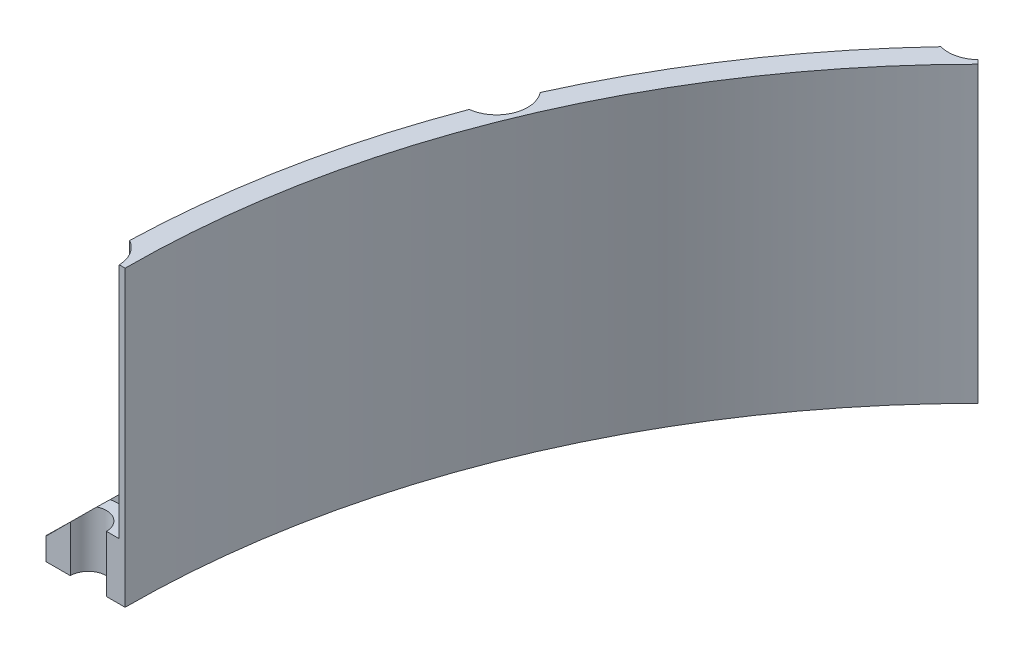
SolidWorks part; units mm, degrees
ref_plane "Front Plane" through (0, 0, 0) normal (0, 0, 1) x (1, 0, 0)
ref_plane "Top Plane" through (0, 0, 0) normal (0, 1, 0) x (1, 0, 0)
ref_plane "Right Plane" through (0, 0, 0) normal (1, 0, 0) x (0, 0, -1)
sketch "Sketch1" plane through (0, 0, 0) normal (0, 1, 0) x (1, 0, 0)
  line L0 (0, 0) -> (-77.15, 0) construction
  line L1 (0, 0) -> (0, 88.5692) construction
  line L2 (-53.3866, 53.3866) -> (-54.5533, 54.5533)
  line L3 (-75.5, 0) -> (-77.15, 0)
  line L4 (0, 0) -> (-104.3217, 43.2115) construction
  line L5 (0, 0) -> (-103.9733, 20.6816) construction
  line L6 (-55.6847, 55.6847) -> (-56.816, 56.816) construction
  line L7 (-56.816, 56.816) -> (-58.3363, 58.3363)
  line L8 (-54.5533, 54.5533) -> (-55.6847, 55.6847) construction
  line L9 (-78.75, 0) -> (-80.35, 0) construction
  line L10 (-80.35, 0) -> (-99.2871, 0) construction
  line L11 (-78.75, 0) -> (-80.35, 0) construction
  line L12 (-80.35, 0) -> (-82.5, 0)
  line L13 (-77.15, 0) -> (-78.75, 0) construction
  line L14 (-77.15, 0) -> (-78.75, 0) construction
  circle A0 centre (0, 0) radius 82.5 construction
  arc A1 (-82.5, 0) -> (-58.3363, 58.3363) centre (0, 0) cw
  arc A2 (-75.5, 0) -> (-53.3866, 53.3866) centre (0, 0) cw
  circle A3 centre (-72.7555, 30.1363) radius 1.6
  circle A4 centre (0, 0) radius 78.75 construction
  circle A5 centre (-77.2368, 15.3634) radius 1.25
  circle A6 centre (-65.4782, 43.7512) radius 1.25
  arc A7 (-80.35, 0) -> (-77.15, 0) centre (-78.75, 0) cw
  arc A8 (-56.816, 56.816) -> (-54.5533, 54.5533) centre (-55.6847, 55.6847) ccw
  arc A9 (-54.5419, 56.8045) -> (-56.816, 56.816) centre (-55.6847, 55.6847) ccw construction
  arc A10 (-54.5533, 54.5533) -> (-54.5419, 56.8045) centre (-55.6847, 55.6847) ccw construction
  arc A11 (-78.7337, -1.5999) -> (-80.35, 0) centre (-78.75, 0) cw construction
  arc A12 (-77.15, 0) -> (-78.7337, -1.5999) centre (-78.75, 0) cw construction
  dimension "D1" = 165
  dimension "D4" = 157.5
  dimension "D5" = 3.2
  dimension "D8" = 2.5
  dimension "D6" = 22.5
  dimension "D3" = 7
extrude "Boss-Extrude1" add sketch "Sketch1" along normal blind 2 contours A1 | A2 L3 A1 L2 region at (-71.209, 0, -29.4957)
sketch "Sketch2" plane through (0, 2, 0) normal (0, 1, 0) x (1, 0, 0)
  line L0 (-75.5, 0) -> (-77.15, 0)
  line L1 (-75.5, 0) -> (-77.15, 0) construction
  line L3 (-54.5533, 54.5533) -> (-53.3866, 53.3866)
  arc A2 (-55.3857, 54.1128) -> (-64.9332, 42.1949) centre (-0.0005, -0.04) ccw
  arc A3 (-77.4605, 0) -> (-54.773, 54.7325) centre (-0.0005, -0.04) ccw construction
  arc A6 (-71.897, 28.7862) -> (-77.4543, 0.9387) centre (-0.0005, -0.04) ccw construction
  arc A7 (-72.0793, 28.3273) -> (-76.1531, 14.1313) centre (-0.0005, -0.04) ccw
  arc A8 (-53.3866, 53.3866) -> (-75.5, 0) centre (0, 0) ccw construction
  arc A9 (-77.4605, 0) -> (-54.773, 54.7325) centre (-0.0005, -0.04) ccw construction
  arc A11 (-77.4605, 0) -> (-54.773, 54.7325) centre (-0.0005, -0.04) ccw construction
  arc A14 (-71.897, 28.7862) -> (-77.4543, 0.9387) centre (-0.0005, -0.04) ccw construction
  arc A15 (-64.9332, 42.1949) -> (-71.1934, 30.4825) centre (-0.0005, -0.04) ccw
  arc A17 (-71.897, 28.7862) -> (-77.4543, 0.9387) centre (-0.0005, -0.04) ccw construction
  arc A18 (-76.1531, 14.1313) -> (-77.4543, 0.9387) centre (-0.0005, -0.04) ccw
  circle A19 centre (-72.7555, 30.1363) radius 1.6 construction
  arc A20 (-71.897, 28.7862) -> (-71.1934, 30.4825) centre (-72.7555, 30.1363) ccw
  circle A21 centre (-77.2368, 15.3634) radius 1.25 construction
  circle A22 centre (-77.2368, 15.3634) radius 1.25 construction
  circle A23 centre (-65.4782, 43.7512) radius 1.25 construction
  circle A24 centre (-65.4782, 43.7512) radius 1.25 construction
  arc A25 (-71.1934, 30.4825) -> (-71.897, 28.7862) centre (-72.7555, 30.1363) ccw construction
  arc A26 (-71.1934, 30.4825) -> (-71.897, 28.7862) centre (-0.0005, -0.04) ccw construction
  arc A27 (-71.897, 28.7862) -> (-72.0793, 28.3273) centre (-0.0005, -0.04) ccw
  arc A28 (-71.1934, 30.4825) -> (-71.897, 28.7862) centre (-0.0005, -0.04) ccw construction
  arc A29 (-71.1934, 30.4825) -> (-71.897, 28.7862) centre (-0.0005, -0.04) ccw construction
  arc A30 (-71.1934, 30.4825) -> (-71.897, 28.7862) centre (-0.0005, -0.04) ccw construction
  arc A31 (-77.15, 0) -> (-80.35, 0) centre (-78.75, 0) ccw construction
  arc A32 (-77.15, 0) -> (-77.4543, 0.9387) centre (-78.75, 0) ccw
  arc A33 (-56.816, 56.816) -> (-54.5533, 54.5533) centre (-55.6847, 55.6847) ccw construction
  arc A34 (-55.3857, 54.1128) -> (-54.5533, 54.5533) centre (-55.6847, 55.6847) ccw
  arc A35 (-55.3857, 54.1128) -> (-71.1934, 30.4825) centre (-0.0005, -0.04) ccw construction
  arc A36 (-55.3857, 54.1128) -> (-71.1934, 30.4825) centre (-0.0005, -0.04) ccw construction
  arc A37 (-55.3857, 54.1128) -> (-71.1934, 30.4825) centre (-0.0005, -0.04) ccw construction
  arc A38 (-56.816, 56.816) -> (-55.3857, 54.1128) centre (-55.6847, 55.6847) ccw construction
  arc A39 (-77.4543, 0.9387) -> (-80.35, 0) centre (-78.75, 0) ccw construction
  arc A40 (-53.3866, 53.3866) -> (-75.5, 0) centre (0, 0) ccw
  dimension "D1" = 2
extrude "Boss-Extrude3" add sketch "Sketch2" along normal blind 24
chamfer "Chamfer2" distance 5 angle 45 1 edges at (-64.383, 2, -43.0291)
sketch "Sketch3" plane through (0, 26, 0) normal (0, 1, 0) x (1, 0, 0)
  line L0 (-0.0005, -0.04) -> (-77.2445, 15.3248) construction
  line L1 (-0.0005, -0.04) -> (-64.8995, -0.04) construction
  line L2 (-0.0005, -0.04) -> (-72.7555, 30.1363) construction
  circle A1 centre (-72.7555, 30.1363) radius 2.75
  circle A2 centre (-78.7653, -0.0771) radius 2.75
  circle A3 centre (-55.6168, 55.7339) radius 2.75
  dimension "D1" = 5.5
  dimension "D2" = 11.25
extrude "Cut-Extrude1" cut sketch "Sketch3" against normal blind 21
